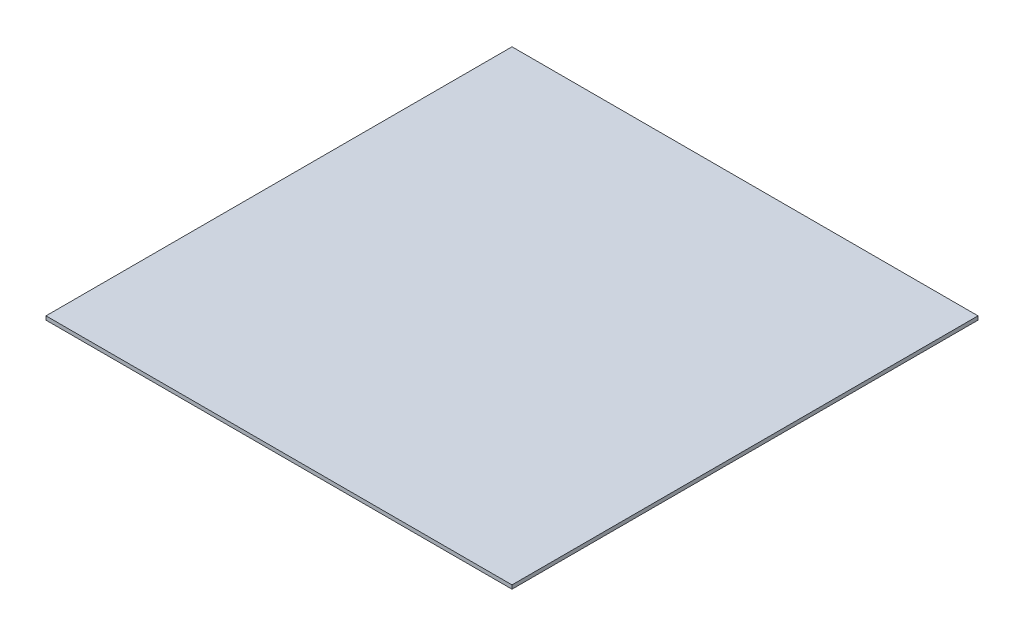
SolidWorks part; units mm, degrees
material "Acrylic (Medium-high impact)"
ref_plane "Front Plane" through (0, 0, 0) normal (0, 0, 1) x (1, 0, 0)
ref_plane "Top Plane" through (0, 0, 0) normal (0, 1, 0) x (1, 0, 0)
ref_plane "Right Plane" through (0, 0, 0) normal (1, 0, 0) x (0, 0, -1)
sketch "Sketch1" plane through (0, 0, 0) normal (0, 1, 0) x (1, 0, 0)
  line L1 (-196.85, -196.85) -> (196.85, -196.85)
  line L2 (-196.85, -196.85) -> (-196.85, 196.85)
  line L3 (-196.85, 196.85) -> (196.85, 196.85)
  line L4 (196.85, -196.85) -> (196.85, 196.85)
  line L5 (-196.85, -196.85) -> (196.85, 196.85) construction
  line L6 (-196.85, 196.85) -> (196.85, -196.85) construction
  point P0 (0, 0)
  dimension "D1" = 393.7
  dimension "D2" = 393.7
extrude "Boss-Extrude1" add sketch "Sketch1" along normal blind 3.175
